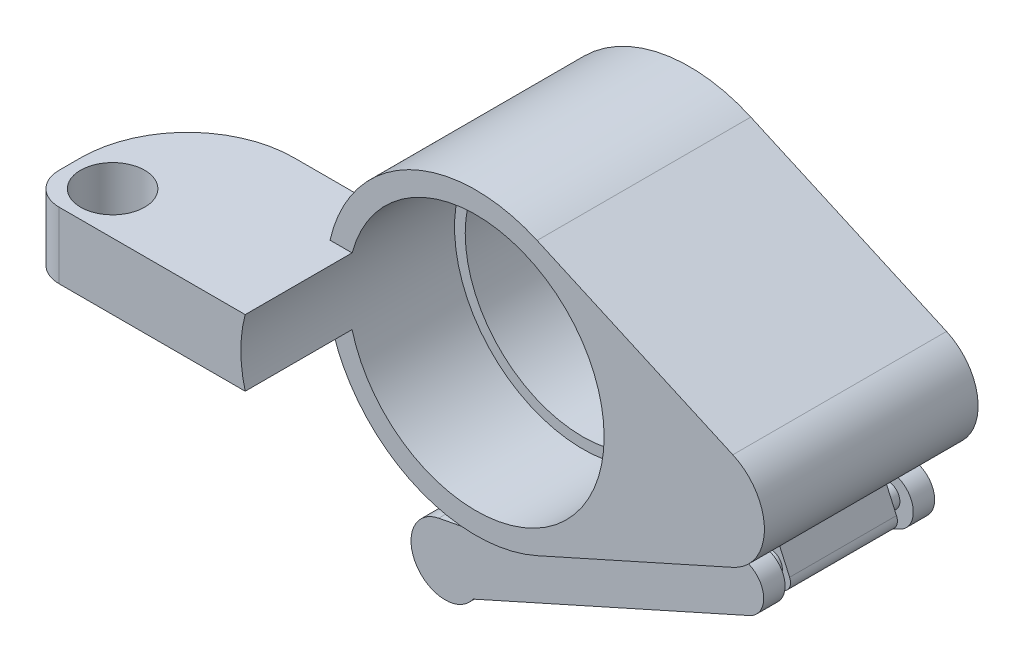
SolidWorks part; units mm, degrees
material "BUTYL"
ref_plane "Plan de face" through (0, 0, 0) normal (0, 0, 1) x (1, 0, 0)
ref_plane "Plan de dessus" through (0, 0, 0) normal (0, 1, 0) x (1, 0, 0)
ref_plane "Plan de droite" through (0, 0, 0) normal (1, 0, 0) x (0, 0, -1)
sketch "Esquisse2" plane through (0, 0, 0) normal (0, 0, 1) x (1, 0, 0)
  line L0 (5.7273, 12.7749) -> (24.0455, 4.5625)
  line L1 (5.7273, -12.7749) -> (24.0455, -4.5625)
  arc A0 (5.7273, 12.7749) -> (5.7273, -12.7749) centre (0, 0) ccw
  arc A1 (24.0455, -4.5625) -> (24.0455, 4.5625) centre (22, 0) ccw
  circle A2 centre (0, 0) radius 11
  dimension "D1" = 14
  dimension "D3" = 5
  dimension "D4" = 22
  dimension "D2" = 22
extrude "Boss.-Extru.1" add sketch "Esquisse2" along normal blind 20
sketch "Esquisse3" plane through (0, 0, 20) normal (0, 0, 1) x (1, 0, 0)
  circle A0 centre (0, 0) radius 12
  circle A1 centre (0, 0) radius 11
  dimension "D1" = 24
  dimension "D2" = 1
extrude "Enlèv. mat.-Extru.1" cut sketch "Esquisse3" against normal blind 10
sketch "Esquisse4" plane through (5.7273, -12.7749, 0) normal (0.4091, -0.9125, 0) x (0.9125, 0.4091, 0)
  line L0 (0, 20) -> (20.0749, 20) construction
  line L1 (16.0749, 15) -> (19.0749, 15)
  line L2 (16.0749, 15) -> (16.0749, 5)
  line L3 (16.0749, 5) -> (19.0749, 5)
  line L4 (19.0749, 15) -> (19.0749, 5)
  line L5 (20.0749, 20) -> (20.0749, 0) construction
  dimension "D1" = 10
  dimension "D2" = 5
  dimension "D3" = 1
  dimension "D4" = 3
extrude "Boss.-Extru.2" add sketch "Esquisse4" along normal blind 4
sketch "Esquisse5" plane through (0, 0, 15) normal (0, 0, 1) x (1, 0, 0)
  line L0 (24.7693, -8.6215) -> (23.133, -4.9716) construction
  line L1 (24.7693, -8.6215) -> (22.0318, -9.8488) construction
  circle A0 centre (22.5824, -7.4102) radius 1.1
  dimension "D3" = 2.2
  dimension "D1" = 1.5
  dimension "D2" = 2
extrude "Boss.-Extru.3" add sketch "Esquisse5" along normal blind 1
sketch "Esquisse6" plane through (7.3636, -16.4249, 0) normal (0.4091, -0.9125, 0) x (0.9125, 0.4091, 0)
  line L0 (16.0749, 10) -> (19.0749, 10) construction
  line L1 (16.0749, 15) -> (16.0749, 5) construction
  line L2 (19.0749, 5) -> (19.0749, 15) construction
ref_plane "Plan1" through (0, 0, 10) normal (0, 0, 1) x (1, 0, 0)
mirror "Symétrie1" about plane through (0, 0, 10) normal (0, 0, 1) of "Boss.-Extru.3"
sketch "Esquisse9" plane through (0, 0, 16) normal (0, 0, 1) x (1, 0, 0)
  line L0 (23.6051, -9.6914) -> (-2.2602, -21.2874)
  line L1 (5.7273, -12.7749) -> (24.0455, -4.5625) construction
  line L2 (-5.4847, -16.3395) -> (-0.9203, -15.4625)
  line L3 (1.2837, -14.767) -> (21.7642, -5.5852)
  line L4 (19.483, -6.6079) -> (21.3239, -10.7141)
  line L5 (22.0318, -9.8488) -> (20.3955, -6.1988) construction
  line L6 (22.5824, -7.4102) -> (23.6622, -9.8186) construction
  arc A0 (-2.2602, -21.2874) -> (-5.4847, -16.3395) centre (-4.8828, -19.4719) cw
  arc A1 (21.7642, -5.5852) -> (23.6051, -9.6914) centre (22.6847, -7.6383) cw
  arc A2 (1.2837, -14.767) -> (-0.9203, -15.4625) centre (-2.8072, -5.6421) cw
  circle M8 centre (22.5824, -7.4102) radius 1.1
  dimension "D1" = 10
  dimension "D2" = 4.5
  dimension "D3" = 30
  dimension "D4" = 1
extrude "Boss.-Extru.5" add sketch "Esquisse9" along normal blind 2 contours A1 L3 L4 L0 M8 | M8 region at (22.4333, -10.1332, 16) region at (22.5824, -7.4102, 16)
extrude "Boss.-Extru.6" add sketch "Esquisse9<4>" against normal up to surface (6 mm away) and the other way blind 2 contours L3 A2 L2 A0 L0 L4 region at (5.89, -15.0189, 16) up to plane "Plan1"
sketch "Esquisse9<4>" plane through (0, 0, 16) normal (0, 0, 1) x (1, 0, 0) same geometry as "Esquisse9"
mirror "Symétrie2" about plane through (0, 0, 10) normal (0, 0, 1) of "Boss.-Extru.5", "Boss.-Extru.6"
fillet "Congé1" radius 1 1 edges at (24.7693, -8.6215, 10)
fillet "Congé2" radius 1 1 edges at (22.0318, -9.8488, 10)
sketch "Esquisse10" plane through (0, 0, 20) normal (0, 0, 1) x (1, 0, 0)
  line L0 (-10.5523, -3.1063) -> (-32, -3.1063)
  line L1 (-32, -3.1063) -> (-32, 3.1063)
  line L2 (-32, 3.1063) -> (-10.5523, 3.1063)
  line L3 (0, 0) -> (-25.0003, 0) construction
  arc A0 (-10.5523, 3.1063) -> (-10.5523, -3.1063) centre (0, 0) ccw
  arc A1 (-13.651, 3.1063) -> (-13.651, -3.1063) centre (0, 0) ccw
  point P5 (-32, 0)
  circle M3 centre (0, 0) radius 12
  arc M4 (5.7273, 12.7749) -> (5.7273, -12.7749) centre (0, 0) ccw
  dimension "D1" = 32
extrude "Boss.-Extru.7" add sketch "Esquisse10" along normal blind 10 contours L3 A0 L2 M4 | L3 A1 L0 M3 region at (-12.8734, -1.5608, 20) region at (-12.8734, 1.5608, 20)
extrude "Boss.-Extru.8" add sketch "Esquisse10<3>" along normal blind 10 and the other way blind 5 contours L3 L2 L1 M4 | A1 L3 L1 L0 region at (-22.9418, 0, 20)
sketch "Esquisse10<3>" plane through (0, 0, 20) normal (0, 0, 1) x (1, 0, 0) same geometry as "Esquisse10"
fillet "Congé3" radius 10 1 edges at (-32, 0, 15)
fillet "Congé4" radius 3 1 edges at (-32, 0, 30)
sketch "Esquisse11" plane through (0, 3.1063, 0) normal (0, 1, 0) x (1, 0, 0)
  line L0 (-29, -30) -> (-11.591, -30) construction
  line L1 (-32, -25) -> (-32, -27) construction
  circle A0 centre (-28, -26) radius 3
  dimension "D1" = 6
  dimension "D2" = 4
  dimension "D3" = 4
extrude "Enlèv. mat.-Extru.2" cut sketch "Esquisse11" against normal up to next
